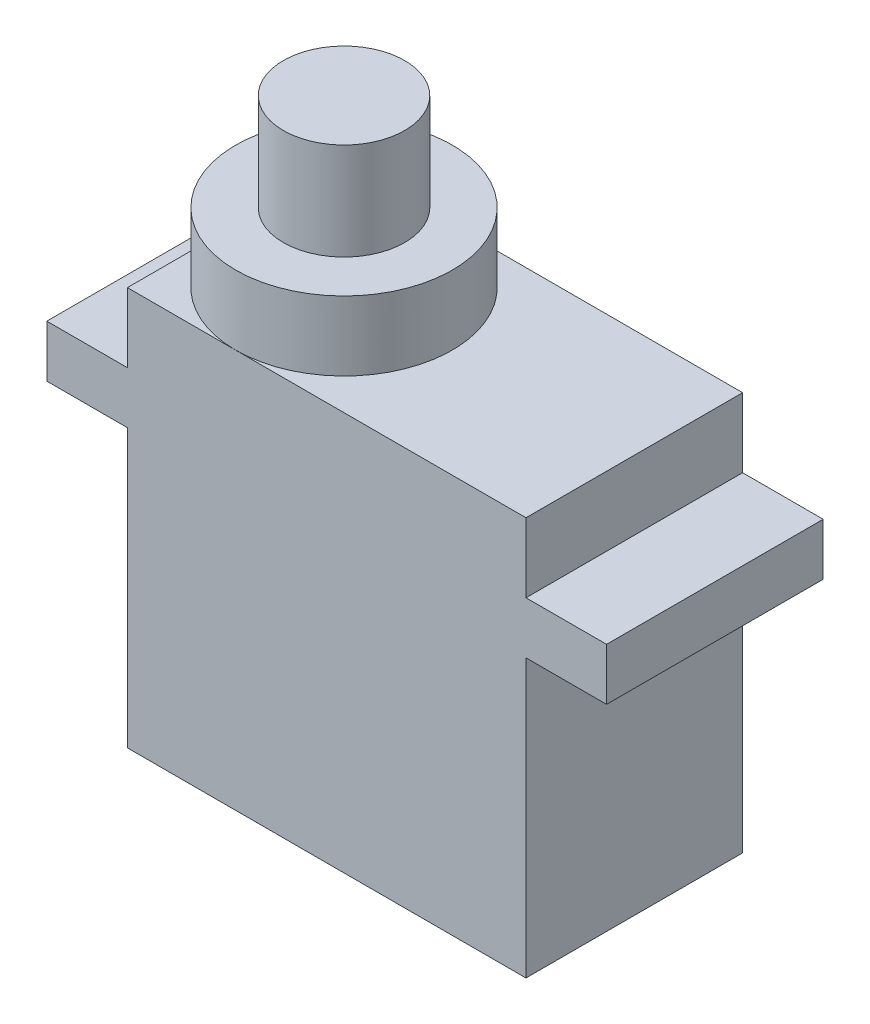
SolidWorks part; units mm, degrees
ref_plane "Płaszczyzna przednia" through (0, 0, 0) normal (0, 0, 1) x (1, 0, 0)
ref_plane "Płaszczyzna górna" through (0, 0, 0) normal (0, 1, 0) x (1, 0, 0)
ref_plane "Płaszczyzna prawa" through (0, 0, 0) normal (1, 0, 0) x (0, 0, -1)
sketch "Sketch1" plane through (0, 0, 0) normal (0, 1, 0) x (1, 0, 0)
  line L0 (-10.7409, 6.2842) -> (-15.3909, 6.2842)
  line L1 (-10.7409, 6.2842) -> (12.2591, 6.2842)
  line L2 (-10.7409, 6.2842) -> (-10.7409, -6.2158)
  line L3 (-10.7409, -6.2158) -> (12.2591, -6.2158)
  line L4 (12.2591, 6.2842) -> (12.2591, -6.2158)
  line L5 (-15.3909, 6.2842) -> (-15.3909, -6.2158)
  line L6 (-15.3909, -6.2158) -> (-10.7409, -6.2158)
  line L7 (12.2591, 6.2842) -> (16.9091, 6.2842)
  line L8 (16.9091, 6.2842) -> (16.9091, -6.2158)
  line L9 (16.9091, -6.2158) -> (12.2591, -6.2158)
  line L10 (0.7591, 13.3848) -> (0.7591, -13.6054) construction
  circle A0 centre (-4.4909, 0.0342) radius 6.25
  circle A1 centre (-4.4909, 0.0342) radius 3.5
  dimension "D4" = 7
  dimension "D1" = 12.5
  dimension "D2" = 23
  dimension "D3" = 32.3
extrude "Boss-Extrude1" add sketch "Sketch1" along normal blind 23 contours A0 L1 L2 | L10 A0 A1 | L1 L10 A0 L3 L4 | L10 A0 L3 | L10 L1 A0 | A0 L10 | A1 | A0 L2 L3 region at (-9.3448, 0, -4.8881) region at (-0.4859, 0, -5.4751) region at (-1.5832, 0, -5.3739) region at (-9.3448, 0, 4.8198) region at (6.6859, 0, -0.0342) region at (1.162, 0, -0.0342) region at (-0.4859, 0, 5.4068) region at (-4.4909, 0, -0.0342)
extrude "Boss-Extrude2" add sketch "Sketch1<3>" along normal blind 3 from offset 16 contours L5 L6 L2 L0 | L9 L8 L7 L4 region at (-13.0659, 0, -0.0342) region at (14.5841, 0, -0.0342)
sketch "Sketch1<3>" plane through (0, 0, 0) normal (0, 1, 0) x (1, 0, 0) same geometry as "Sketch1"
extrude "Boss-Extrude3" add sketch "Sketch1<4>" along normal blind 4 from surface contours A0 starting at face at (0.7591, 23, -0.0342)
sketch "Sketch1<4>" plane through (0, 0, 0) normal (0, 1, 0) x (1, 0, 0) same geometry as "Sketch1"
extrude "Boss-Extrude4" add sketch "Sketch1<5>" along normal blind 5.6 from surface contours A1 starting at face at (-4.4909, 27, 6.2158)
sketch "Sketch1<5>" plane through (0, 0, 0) normal (0, 1, 0) x (1, 0, 0) same geometry as "Sketch1"
